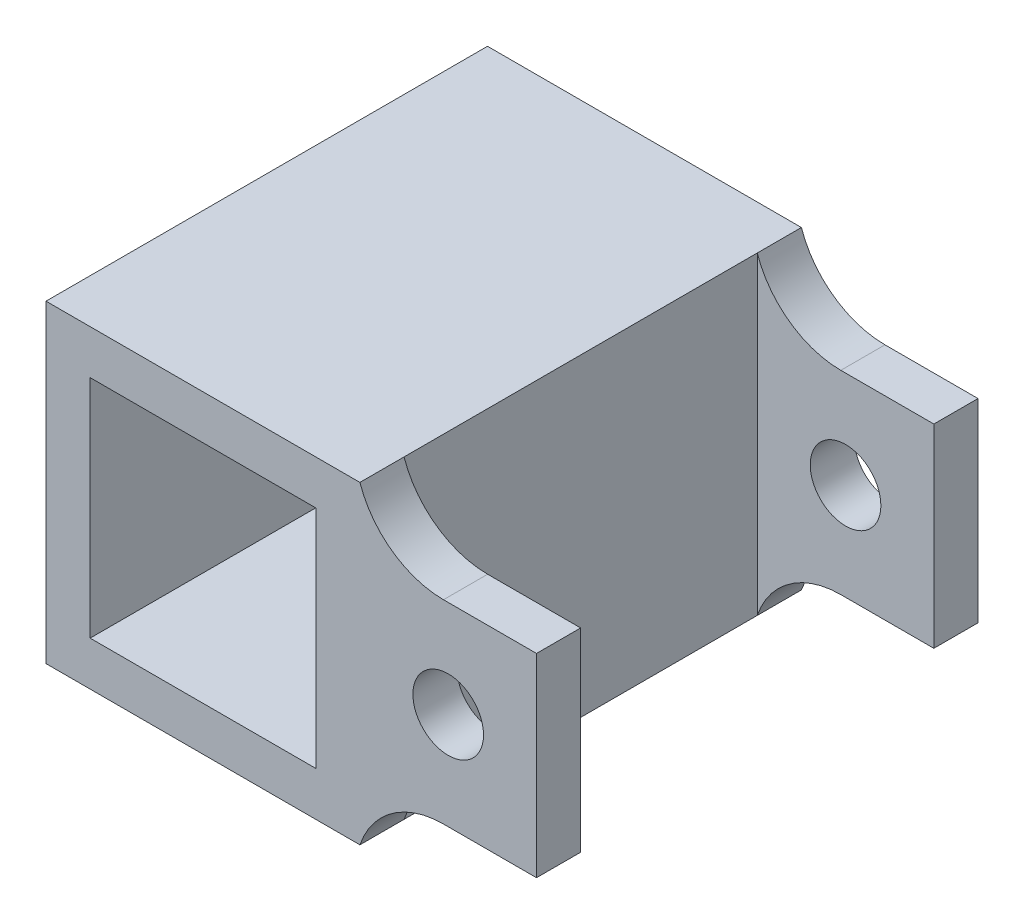
SolidWorks part; units mm, degrees
ref_plane "Front Plane" through (0, 0, 0) normal (0, 0, 1) x (1, 0, 0)
ref_plane "Top Plane" through (0, 0, 0) normal (0, 1, 0) x (1, 0, 0)
ref_plane "Right Plane" through (0, 0, 0) normal (1, 0, 0) x (0, 0, -1)
sketch "Sketch1" plane through (0, 0, 0) normal (0, 0, 1) x (1, 0, 0)
  line L1 (-12.775, -12.775) -> (12.775, -12.775)
  line L2 (-12.775, -12.775) -> (-12.775, 12.775)
  line L3 (-12.775, 12.775) -> (12.775, 12.775)
  line L4 (12.775, -12.775) -> (12.775, 12.775)
  line L5 (-12.775, -12.775) -> (12.775, 12.775) construction
  line L6 (-12.775, 12.775) -> (12.775, -12.775) construction
  line L7 (17.775, -17.775) -> (-17.775, -17.775)
  line L8 (17.775, -17.775) -> (17.775, 17.775)
  line L9 (17.775, 17.775) -> (-17.775, 17.775)
  line L10 (-17.775, -17.775) -> (-17.775, 17.775)
  line L11 (17.775, -17.775) -> (-17.775, 17.775) construction
  line L12 (17.775, 17.775) -> (-17.775, -17.775) construction
  point P0 (0, 0)
  point P6 (0, 0)
  dimension "D1" = 25.55
  dimension "D2" = 5
extrude "Boss-Extrude1" add sketch "Sketch1" along normal mid plane 50
sketch "Sketch2" plane through (-17.775, 0, 0) normal (-1, 0, 0) x (0, 0, 1)
  line L0 (0, 17.775) -> (0, -19.9682) construction
  line L1 (25, 17.775) -> (-25, 17.775) construction
  line L2 (-15.6, -14.775) -> (15.6, -14.775) construction
  line L3 (25, -17.775) -> (-25, -17.775) construction
  circle A0 centre (-15.6, -14.775) radius 1.25
  circle A1 centre (15.6, -14.775) radius 1.25
  circle A2 centre (-15.6, -8.375) radius 1.25
  circle A3 centre (15.6, -8.375) radius 1.25
  circle A4 centre (-15.6, -1.975) radius 1.25
  circle A5 centre (15.6, -1.975) radius 1.25
  circle A6 centre (-15.6, 4.425) radius 1.25
  circle A7 centre (15.6, 4.425) radius 1.25
  circle A8 centre (-15.6, 10.825) radius 1.25
  circle A9 centre (15.6, 10.825) radius 1.25
  dimension "D2" = 2.5
  dimension "D1" = 31.2
  dimension "D3" = 3
  dimension "D5" = 6.4
  dimension "D4" = 5
extrude "Cut-Extrude1" cut sketch "Sketch2" against normal mid plane 8
sketch "Sketch3" plane through (0, 0, 25) normal (0, 0, 1) x (1, 0, 0)
  line L0 (17.775, -17.775) -> (17.775, 17.775) construction
  line L1 (37.775, 11) -> (17.775, 11)
  line L2 (37.775, 11) -> (37.775, -11)
  line L3 (37.775, -11) -> (17.775, -11)
  line L4 (17.775, 11) -> (17.775, -11)
  line L5 (37.775, 11) -> (17.775, -11) construction
  line L6 (37.775, -11) -> (17.775, 11) construction
  line L7 (12.775, -12.775) -> (12.775, 12.775) construction
  circle A0 centre (27.775, 0) radius 4
  point P0 (27.775, 0)
  dimension "D3" = 8
  dimension "D1" = 25
  dimension "D2" = 22
extrude "Boss-Extrude2" add sketch "Sketch3" against normal blind 5
fillet "Fillet1" radius 10 2 edges at (17.775, -11, 22.5) (17.775, 11, 22.5)
mirror "Mirror2" about plane through (0, 0, 0) normal (0, 0, 1) of "Fillet1", "Boss-Extrude2"
